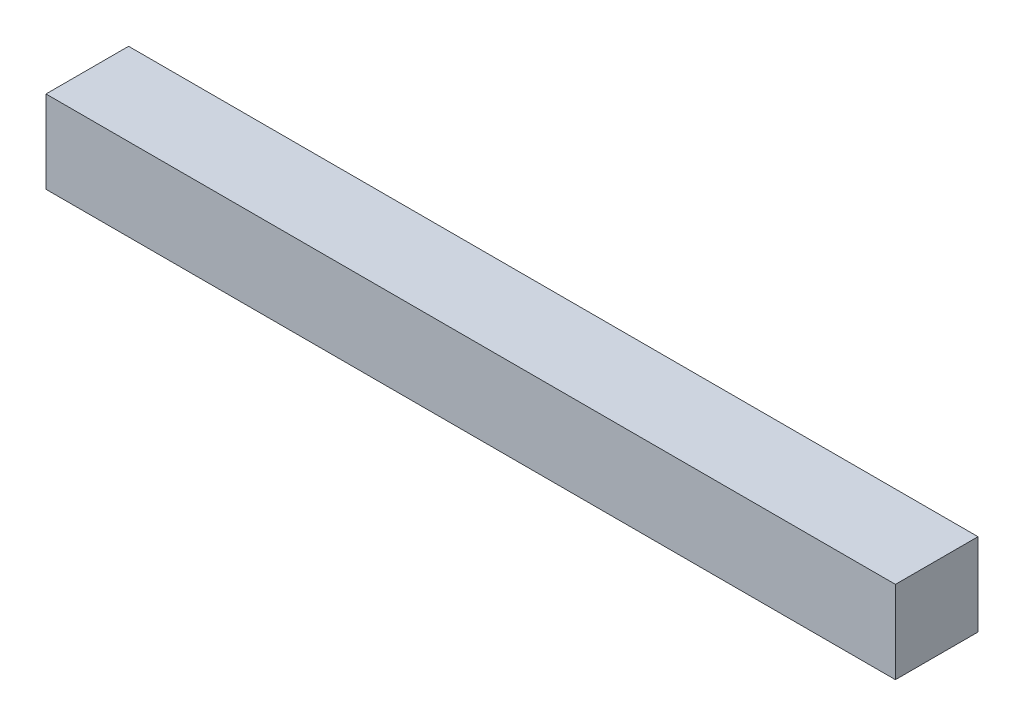
SolidWorks part; units mm, degrees
material "Oak"
ref_plane "Alzado" through (0, 0, 0) normal (0, 0, 1) x (1, 0, 0)
ref_plane "Planta" through (0, 0, 0) normal (0, 1, 0) x (1, 0, 0)
ref_plane "Vista lateral" through (0, 0, 0) normal (1, 0, 0) x (0, 0, -1)
sketch "Sketch1" plane through (0, 0, 0) normal (1, 0, 0) x (0, 0, -1)
  line L0 (-7, 7) -> (7, -7) construction
  line L1 (-7, 7) -> (7, 7)
  line L2 (-7, 7) -> (-7, -7)
  line L3 (-7, -7) -> (7, -7)
  line L4 (7, 7) -> (7, -7)
  dimension "D1" = 14
extrude "Boss-Extrude1" add sketch "Sketch1" along normal blind 144
